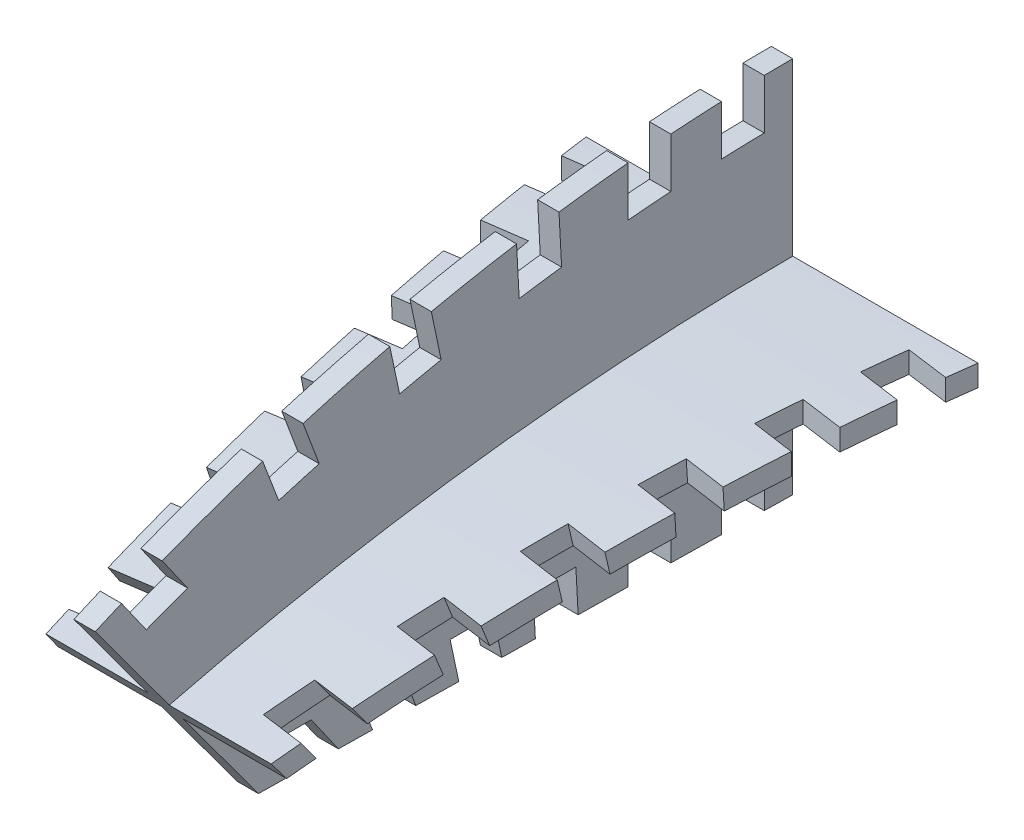
SolidWorks part; units mm, degrees
ref_plane "Alzado" through (0, 0, 0) normal (0, 0, 1) x (1, 0, 0)
ref_plane "Planta" through (0, 0, 0) normal (0, 1, 0) x (1, 0, 0)
ref_plane "Vista lateral" through (0, 0, 0) normal (1, 0, 0) x (0, 0, -1)
sketch "Croquis1" plane through (0, 0, 0) normal (1, 0, 0) x (0, 0, -1)
  line L0 (-88.9729, -11.2369) -> (-77.0017, -28) construction
  line L1 (-77.0017, -28) -> (0, -29.2) construction
  line L2 (0, -29.2) -> (0, 29.2) construction
  line L3 (-88.9729, -11.2369) -> (-100.9389, 5.5167) construction
  line L4 (-77.0017, -28) -> (-146.4619, -28) construction
  line L5 (-146.4619, -28) -> (-100.9389, 5.5167) construction
  arc A1 (0, 0) -> (-138.7663, -28) centre (0, -357.859) ccw
  arc A2 (0, 29.2) -> (-100.9389, 5.5167) centre (0, -197.7439) ccw construction
  point P0 (-88.9729, -11.2369)
  point P1 (0, 0)
  point P10 (0, 29.2)
  dimension "D3" = 226.9439
  dimension "D5" = 77.0017
  dimension "D1" = 20.5881
  dimension "D2" = 58.4
  dimension "D6" = 11.9712
  dimension "D7" = 16.5745
  dimension "D8" = 16.7536
  dimension "D9" = 29.2
  dimension "D10" = 29.2
sketch "Croquis3" plane through (0, 0, 0) normal (0, 0, 1) x (1, 0, 0)
  line L0 (1.5, 1.5) -> (27.5, 1.5)
  line L1 (-1.5, 27.5) -> (1.5, 27.5)
  line L2 (-1.5, 27.5) -> (-1.5, 1.5)
  line L3 (-1.5, -27.5) -> (1.5, -27.5)
  line L4 (1.5, 27.5) -> (1.5, 1.5)
  line L5 (-27.5, 1.5) -> (-1.5, 1.5)
  line L6 (-27.5, 1.5) -> (-27.5, -1.5)
  line L7 (-27.5, -1.5) -> (-1.5, -1.5)
  line L8 (27.5, 1.5) -> (27.5, -1.5)
  line L9 (1.5, -1.5) -> (27.5, -1.5)
  line L10 (1.5, -1.5) -> (1.5, -27.5)
  line L11 (-1.5, -1.5) -> (-1.5, -27.5)
  circle A0 centre (0, 0) radius 29.2 construction
  point P14 (0, 0)
  point P15 (0, -27.5)
  point P16 (27.5, 0)
  dimension "D1" = 3
  dimension "D2" = 3
  dimension "D3" = 55
  dimension "D4" = 55
  dimension "D5" = 26
  dimension "D6" = 26
sweep "Barrer1" add profiles "Croquis3" path "Croquis1"
sketch "Croquis4" plane through (0, 0, 0) normal (1, 0, 0) x (0, 0, -1)
  line L0 (0, -27.5) -> (-74.9909, -26.3311)
  line L1 (-74.9909, -26.3311) -> (-97.8925, 4.7958)
  line L2 (-88.9729, -11.2369) -> (-100.9389, 5.5167) construction
  line L3 (0, 25.5) -> (0, -27.5)
  line L4 (0, -29.2) -> (0, 29.2) construction
  line L5 (-77.0017, -28) -> (0, -29.2) construction
  arc A0 (0, 29.2) -> (-100.9389, 5.5167) centre (0, -197.7439) ccw construction
  arc A1 (0, 25.5) -> (-97.8925, 4.7958) centre (0, -216.277) ccw
  point P5 (0, 27.5)
  point P12 (-98.9573, 6.4888)
  point P18 (0, 0)
  point P20 (0, 0)
  dimension "D3" = 2
  dimension "D1" = 75
  dimension "D2" = 2.06
  dimension "D4" = 2
  dimension "D5" = 22.9017
  dimension "D6" = 1.7
extrude "Cortar-Extruir1" cut sketch "Croquis4" against normal mid plane 160 flip side to cut
ref_plane "Plano1" through (0, 5.5167, 0) normal (0, 1, 0) x (1, 0, 0)
sketch "Croquis6" plane through (0, 5.5167, 0) normal (0, 1, 0) x (1, 0, 0)
  line L0 (-14, -100.9389) -> (14, -100.9389)
  line L1 (-27.5, 0) -> (27.5, 0)
  line L2 (27.5, 0) -> (14, -100.9389)
  line L3 (-27.5, 0) -> (-14, -100.9389)
  point P0 (-27.5, 0)
  point P4 (0, -100.9389)
  point P6 (27.5, 0)
  dimension "D1" = 28
extrude "Cortar-Extruir2" cut sketch "Croquis6" against normal blind 160 flip side to cut
sketch "Croquis7" plane through (0, 0, 0) normal (1, 0, 0) x (0, 0, -1)
  line L16 (-39.162, 29.8871) -> (-38.3948, 15.5341)
  line L29 (-95.9988, 8.9492) -> (-90.7341, 1.4535)
  line L30 (-77.0017, -28) -> (0, -29.2) construction
  line L31 (-69.9704, -28.1096) -> (-62.5572, -28.2251)
  line L32 (-62.5572, -28.2251) -> (-67.5899, -21.0596)
  line L33 (-91.0888, 12.3977) -> (-95.9988, 8.9492)
  line L46 (-23.1075, 31.5352) -> (-23.1075, 17.4298)
  line L47 (-23.1075, -32.5897) -> (-17.1075, -32.5897)
  line L48 (-17.1075, -32.5897) -> (-17.1075, -21.0596)
  line L49 (-17.1075, 31.5352) -> (-23.1075, 31.5352)
  line L50 (-9.9979, 30.3517) -> (-9.9979, 18.3)
  line L51 (-9.9979, -32.2098) -> (-3.9979, -32.2098)
  line L52 (-3.9979, -32.2098) -> (-3.9979, -21.0596)
  line L53 (-3.9979, 30.3517) -> (-9.9979, 30.3517)
  line L54 (-35.7091, -34.7057) -> (-29.7091, -34.7057)
  line L55 (-29.7091, -34.7057) -> (-30.4386, -21.0596)
  line L56 (-33.162, 29.8871) -> (-39.162, 29.8871)
  line L57 (-78.1222, 23.5232) -> (-72.1409, 7.8652)
  line L58 (-56.7523, -32.4193) -> (-50.7523, -32.4193)
  line L59 (-50.7523, -32.4193) -> (-55.0089, -21.0596)
  line L60 (-72.5037, 25.6286) -> (-78.1222, 23.5232)
  line L65 (-58.9179, 29.9464) -> (-55.1767, 12.3351)
  line L66 (-45.8424, -31.6042) -> (-39.8424, -31.6042)
  line L67 (-39.8424, -31.6042) -> (-42.06, -21.0596)
  line L68 (-53.0464, 31.1812) -> (-58.9179, 29.9464)
  line L69 (-74.922, -21.0596) -> (-67.5899, -21.0596)
  line L70 (-97.8925, 4.7958) -> (-74.9909, -26.3311) construction
  line L71 (-74.9909, -26.3311) -> (0, -27.5) construction
  line L72 (0, -27.5) -> (0, 18.5) construction
  line L73 (-61.0917, -21.0596) -> (-55.0089, -21.0596)
  line L74 (-84.9316, 3.6311) -> (-91.0888, 12.3977)
  line L75 (-74.922, -21.0596) -> (-69.9704, -28.1096)
  line L76 (-66.4616, 9.5039) -> (-72.5037, 25.6286)
  line L77 (-61.0917, -21.0596) -> (-56.7523, -32.4193)
  line L78 (-48.0825, -21.0596) -> (-45.8424, -31.6042)
  line L79 (-48.0825, -21.0596) -> (-42.06, -21.0596)
  line L80 (-49.3451, 13.5817) -> (-53.0464, 31.1812)
  line L81 (-36.4386, -21.0596) -> (-35.7091, -34.7057)
  line L82 (-32.4403, 16.3863) -> (-33.162, 29.8871)
  line L83 (-36.4386, -21.0596) -> (-30.4386, -21.0596)
  line L84 (-23.1075, -21.0596) -> (-17.1075, -21.0596)
  line L85 (-23.1075, -21.0596) -> (-23.1075, -32.5897)
  line L86 (-17.1075, 17.914) -> (-17.1075, 31.5352)
  line L87 (-9.9979, -21.0596) -> (-3.9979, -21.0596)
  line L88 (-9.9979, -21.0596) -> (-9.9979, -32.2098)
  line L89 (-3.9979, 18.468) -> (-3.9979, 30.3517)
  line L90 (0, -29.2) -> (0, 29.2) construction
  line L91 (-76.9774, -23.6311) -> (0, -24.8) construction
  arc A0 (-84.9316, 3.6311) -> (-90.7341, 1.4535) centre (0, -231.5) ccw
  arc A1 (-3.9979, 18.468) -> (-9.9979, 18.3) centre (0, -231.5) ccw
  arc A2 (-66.4616, 9.5039) -> (-72.1409, 7.8652) centre (0, -231.5) ccw
  arc A3 (-49.3451, 13.5817) -> (-55.1767, 12.3351) centre (0, -231.5) ccw
  arc A4 (-32.4403, 16.3863) -> (-38.3948, 15.5341) centre (0, -231.5) ccw
  arc A5 (-17.1075, 17.914) -> (-23.1075, 17.4298) centre (0, -231.5) ccw
  arc A6 (-3.9979, 22.4666) -> (-96.1147, 2.3793) centre (0, -217.126) ccw construction
  point P60 (-89.5408, 5.142)
  point P61 (-68.838, -23.7547)
  point P62 (-70.6274, 11.8552)
  point P63 (-53.0828, 16.5465)
  point P64 (-35.7014, 19.8255)
  point P65 (-56.7557, -23.9382)
  point P66 (-44.6414, -24.1221)
  point P67 (-33.1709, -24.2963)
  point P68 (-20.3112, 21.6376)
  point P69 (-6.8634, 22.4017)
  point P70 (-20.2867, -24.4919)
  point P71 (-6.8441, -24.6961)
  point P72 (0, 25.5)
  point P73 (-96.1147, 2.3793)
  point P75 (0, 0)
  point P76 (0, 0)
  point P77 (0, 0)
  point P78 (0, 0)
  point P79 (0, 22.5)
  point P80 (0, 0)
  dimension "D11" = 500
  dimension "D1" = 6
  dimension "D2" = 6
  dimension "D3" = 6
  dimension "D4" = 6
  dimension "D5" = 6
  dimension "D6" = 6
  dimension "D7" = 6
  dimension "D8" = 6
  dimension "D9" = 6
  dimension "D10" = 6
  dimension "D12" = 230
  dimension "D13" = 3
  dimension "D14" = 3
  dimension "D15" = 3.9979
  dimension "D16" = 2.7
  dimension "D17" = 2.7
  dimension "D18" = 35.5475
  dimension "D19" = 38.3874
  dimension "D20" = 41.5354
  dimension "D21" = 44.1943
  dimension "D22" = 46.1296
  dimension "D23" = 47.0978
extrude "Cortar-Extruir3" cut sketch "Croquis7" against normal mid plane 160
sketch "Croquis9" plane through (27.0167, 0, 3.6133) normal (0.9912, 0, 0.1326) x (0.1326, 0, -0.9912)
  line L25 (-87.8938, 1.4486) -> (-71.9432, -21.062)
  line L26 (-71.9432, -21.062) -> (-64.4966, -21.062)
  line L27 (-64.4966, -21.062) -> (-82.0093, 3.653)
  line L45 (-82.0093, 3.653) -> (-87.8938, 1.4486)
  line L46 (-69.1555, 7.892) -> (-57.9934, -21.0619)
  line L47 (-57.9934, -21.0619) -> (-51.9499, -21.0619)
  line L48 (-51.9499, -21.0619) -> (-63.4064, 9.5191)
  line L49 (-63.4064, 9.5191) -> (-69.1555, 7.892)
  line L50 (-52.034, 12.3501) -> (-44.8638, -21.1855)
  line L51 (-44.8638, -21.1855) -> (-38.7632, -21.1855)
  line L52 (-38.7632, -21.1855) -> (-46.1378, 13.5825)
  line L53 (-46.1378, 13.5825) -> (-52.034, 12.3501)
  line L54 (-35.0905, 15.5475) -> (-29.0851, 16.4008)
  line L55 (-29.0851, 16.4008) -> (-27.0583, -21.0661)
  line L56 (-27.0583, -21.0661) -> (-33.121, -21.0661)
  line L57 (-33.121, -21.0661) -> (-35.0905, 15.5475)
  line L58 (-19.6681, 17.4468) -> (-13.6118, 17.9615)
  line L59 (-13.6118, 17.9615) -> (-13.6118, -21.2078)
  line L60 (-13.6118, -21.2078) -> (-19.6681, -21.2078)
  line L61 (-19.6681, -21.2078) -> (-19.6681, 17.4468)
  line L62 (-6.4424, 18.3308) -> (-0.3889, 18.5296)
  line L63 (-0.3889, 18.5296) -> (-0.3889, -21.0344)
  line L64 (-0.3889, -21.0344) -> (-6.4424, -21.2331)
  line L65 (-6.4424, -21.2331) -> (-6.4424, 18.3308)
  point P22 (-82.046, 3.6384)
  point P25 (-87.8938, 1.4486)
  point P26 (-64.5478, -21.0668)
  point P27 (-71.9432, -21.062)
  point P28 (0, 0)
  point P29 (-51.8392, -21.0678)
  point P30 (-57.9934, -21.0619)
  point P31 (0, 0)
  point P32 (-63.4064, 9.5191)
  point P33 (0, 0)
  point P34 (-69.1555, 7.892)
  point P35 (-46.1378, 13.5825)
  point P36 (-44.8638, -21.1855)
  point P37 (0, 0)
  point P38 (-29.0851, 16.4008)
  point P39 (-19.6681, 17.4468)
  point P40 (-13.6146, 17.9612)
  point P41 (-13.6118, -21.2078)
  point P42 (-0.3873, -21.2078)
  point P43 (0, 0)
  point P44 (-0.3889, 18.5296)
extrude "Cortar-Extruir4" cut sketch "Croquis9" against normal blind 6
mirror "Simetría1" about plane through (0, 0, 0) normal (1, 0, 0) of "Cortar-Extruir4"
sketch "Croquis10" plane through (0, 0, 0) normal (0, 1, 0) x (1, 0, 0)
  line L0 (-24.3957, 0) -> (-12.1468, -87.5086) construction
  line L1 (-1.5, 0) -> (-27.5, 0) construction
  line L2 (-15.7962, -87.5086) -> (-1.5, -87.5086) construction
  line L3 (0, -32.12) -> (0, 32.12) construction
  line L4 (24.3957, 0) -> (12.1468, -87.5086) construction
  point P6 (-23.4585, -6.6957)
  point P7 (-21.5466, -20.3544)
  point P8 (-19.5964, -34.2871)
  point P9 (-17.6104, -48.4755)
  point P10 (-15.472, -63.7531)
  point P11 (-13.1639, -80.2426)
  point P16 (13.1639, -80.2426)
  point P17 (15.472, -63.7531)
  point P18 (17.6104, -48.4755)
  point P19 (19.5964, -34.2871)
  point P20 (21.5466, -20.3544)
  point P21 (23.4585, -6.6957)
  dimension "D1" = 26.3278
  dimension "D2" = 30.9439
  dimension "D3" = 35.2208
  dimension "D4" = 39.1928
  dimension "D5" = 43.0932
  dimension "D6" = 46.9169
